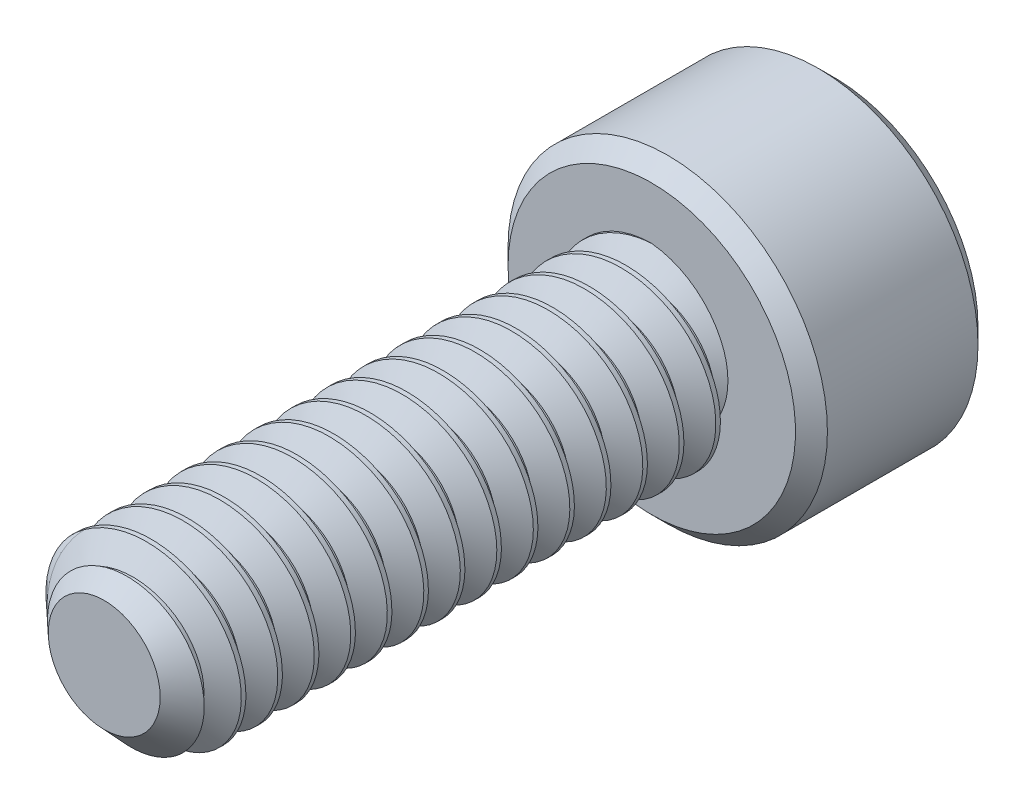
SolidWorks part; units mm, degrees
material "AISI 304"
ref_plane "Front Plane" through (0, 0, 0) normal (0, 0, 1) x (1, 0, 0)
ref_plane "Top Plane" through (0, 0, 0) normal (0, 1, 0) x (1, 0, 0)
ref_plane "Right Plane" through (0, 0, 0) normal (1, 0, 0) x (0, 0, -1)
sketch "Sketch1" plane through (0, 0, 0) normal (0, 0, 1) x (1, 0, 0)
  circle A0 centre (0, 0) radius 2
  dimension "OD" = 4
extrude "Extrude1" add sketch "Sketch1" against normal blind 12
sketch "Sketch2" plane through (0, 0, 0) normal (0, 0, 1) x (1, 0, 0)
  circle A0 centre (0, 0) radius 2 construction
  circle A1 centre (0, 0) radius 2
curve "Helix/Spiral1" pitch 0.8 height 12.8 turns 16 parameters "pitch"=0.8
sketch "Sketch3" plane through (0, 0, 0) normal (1, 0, 0) x (0, 0, -1)
  line L0 (-0.7, 2) -> (-0.4, 1.4804)
  line L1 (-0.4, 1.4804) -> (-0.3, 1.4804)
  line L2 (-0.3, 1.4804) -> (0, 2)
  line L3 (-0.7, 2) -> (0, 2)
  line L4 (-0.35, 2) -> (-0.35, 1.4804) construction
  line L5 (-0.55, 1.7402) -> (-0.15, 1.7402) construction
  line L6 (0, 2) -> (0, -2) construction
  dimension "D1" = 0.1
  dimension "D2" = 0.4
  dimension "D3" = 60
sweep "Cut-Sweep1" cut profiles "Sketch3" path "Helix/Spiral1"
sketch "Sketch4" plane through (0, 0, 0) normal (1, 0, 0) x (0, 0, -1)
  line L0 (0.7214, 2) -> (0, 1.2264)
  line L1 (0, 1.2264) -> (0, 2)
  line L2 (0.7214, 2) -> (0, 2)
  line L3 (-0.7, 2) -> (0, 2) construction
  line L4 (0, 0) -> (7.0209, 0) construction
  dimension "D1" = 47
  dimension "D2" = 0.254
revolve "Cut-Revolve1" cut sketch "Sketch4" angle 360 about L4
sketch "Sketch5" plane through (0, 0, 0) normal (1, 0, 0) x (0, 0, -1)
  line L0 (12, -1.4947) -> (12, 1.4271) construction
  line L1 (12, 2.127) -> (28.1202, 2.127)
  line L2 (12, 2.127) -> (12, 0)
  line L3 (12, 0) -> (28, 0)
  line L4 (28, 1.7968) -> (28, 0)
  line L5 (28.1202, 2.127) -> (28, 1.7968)
  line L6 (0, 0) -> (9.9695, 0) construction
  point P3 (28, 2.127)
  point P10 (28, 2.127)
  dimension "D1" = 0.3302
  dimension "Thread min" = 28
  dimension "D2" = 0.127
  dimension "D3" = 20
revolve "partially thread" [suppressed] add sketch "Sketch5" angle 360 about L6
sketch "Sketch6" plane through (0, 0, -12) normal (0, 0, -1) x (-1, 0, 0)
  circle A0 centre (0, 0) radius 3.5
  dimension "head dia" = 7
extrude "Extrude2" add sketch "Sketch6" along normal blind 4
sketch "Sketch7" plane through (0, 0, -16) normal (0, 0, -1) x (-1, 0, 0)
  line L1 (0, 1.7321) -> (-1.5, 0.866)
  line L2 (-1.5, 0.866) -> (-1.5, -0.866)
  line L3 (-1.5, -0.866) -> (0, -1.7321)
  line L4 (0, -1.7321) -> (1.5, -0.866)
  line L5 (1.5, -0.866) -> (1.5, 0.866)
  line L6 (1.5, 0.866) -> (0, 1.7321)
  circle A0 centre (0, 0) radius 1.5 construction
  dimension "hex dia" = 3
extrude "Cut-Extrude1" cut sketch "Sketch7" against normal blind 2.25
sketch "Sketch8" plane through (0, 0, -16) normal (0, 0, -1) x (-1, 0, 0)
  circle A0 centre (0, 0) radius 1.7321
extrude "Cut-Extrude2" cut sketch "Sketch8" against normal through all draft 45
chamfer "Chamfer1" distance 0.35 angle 45 2 edges at (-3.5, 0, -16) (-3.5, 0, -12)
sketch "Sketch9" plane through (0, 0, 0) normal (1, 0, 0) x (0, 0, -1)
  line L0 (0, 2) -> (0, -2) construction
  line L1 (4.4, 2) -> (4.4, -2) construction
  dimension "D1" = 4.4
  dimension "D4" = 0.635
  dimension "D5" = 0.3302
equation "\"D3@Helix/Spiral1\" = \"screw length@Extrude1\"+\"pitch@Helix/Spiral1\""
equation "\"D1@Sketch3\" = \"pitch@Helix/Spiral1\"*.125"
equation "\"D2@Sketch3\" = \"pitch@Helix/Spiral1\"*.5"
equation "\"D1@Cut-Extrude1\" = \"hex dia@Sketch7\"*.75"
equation "\"D1@Chamfer1\" = \"head dia@Sketch6\"*.05"
equation "\"D1@Sketch9\" = \"pitch@Helix/Spiral1\"*5.5"
